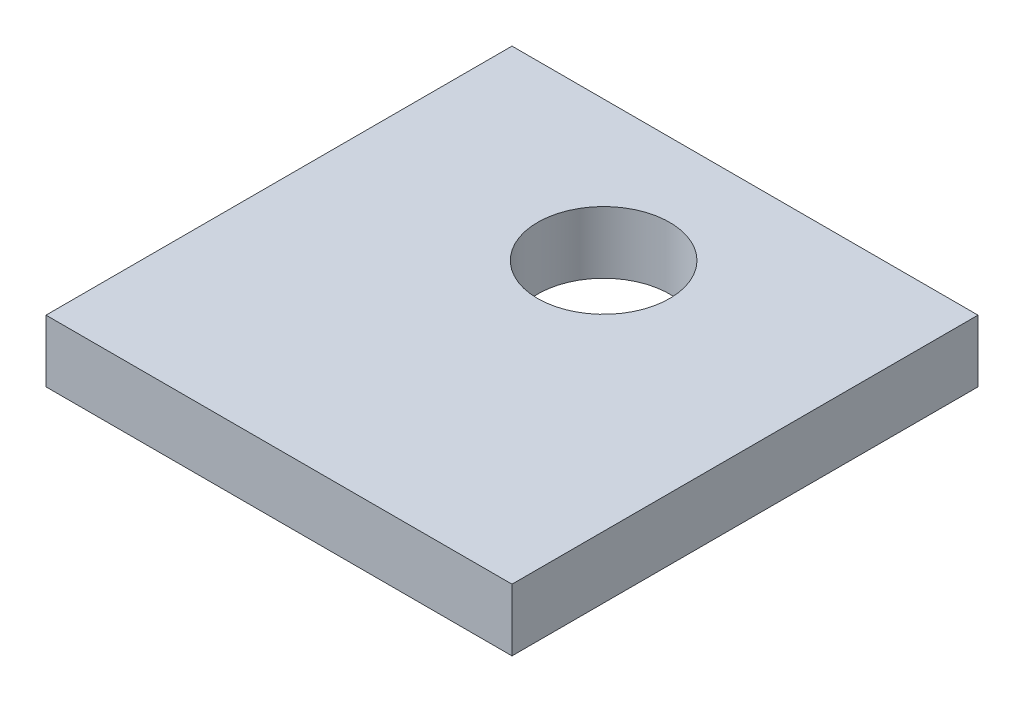
SolidWorks part; units mm, degrees
ref_plane "Front" through (0, 0, 0) normal (0, 0, 1) x (1, 0, 0)
ref_plane "Top" through (0, 0, 0) normal (0, 1, 0) x (1, 0, 0)
ref_plane "Right" through (0, 0, 0) normal (1, 0, 0) x (0, 0, -1)
sketch "Sketch1" plane through (0, 0, 0) normal (0, 1, 0) x (1, 0, 0)
  line L1 (-15, -15) -> (15, -15)
  line L2 (-15, -15) -> (-15, 15)
  line L3 (-15, 15) -> (15, 15)
  line L4 (15, -15) -> (15, 15)
  line L5 (-15, -15) -> (15, 15) construction
  line L6 (-15, 15) -> (15, -15) construction
  point P0 (0, 0)
  dimension "D1" = 30
  dimension "D2" = 30
extrude "Boss-Extrude1" add sketch "Sketch1" along normal mid plane 4
sketch "Sketch2" plane through (0, 2, 0) normal (0, 1, 0) x (1, 0, 0)
  circle A0 centre (-0.1, 6) radius 4.25
  circle A1 centre (-0.1, 6) radius 4 construction
  dimension "D1" = 8.5
extrude "Cut-Extrude1" cut sketch "Sketch2" against normal through all
